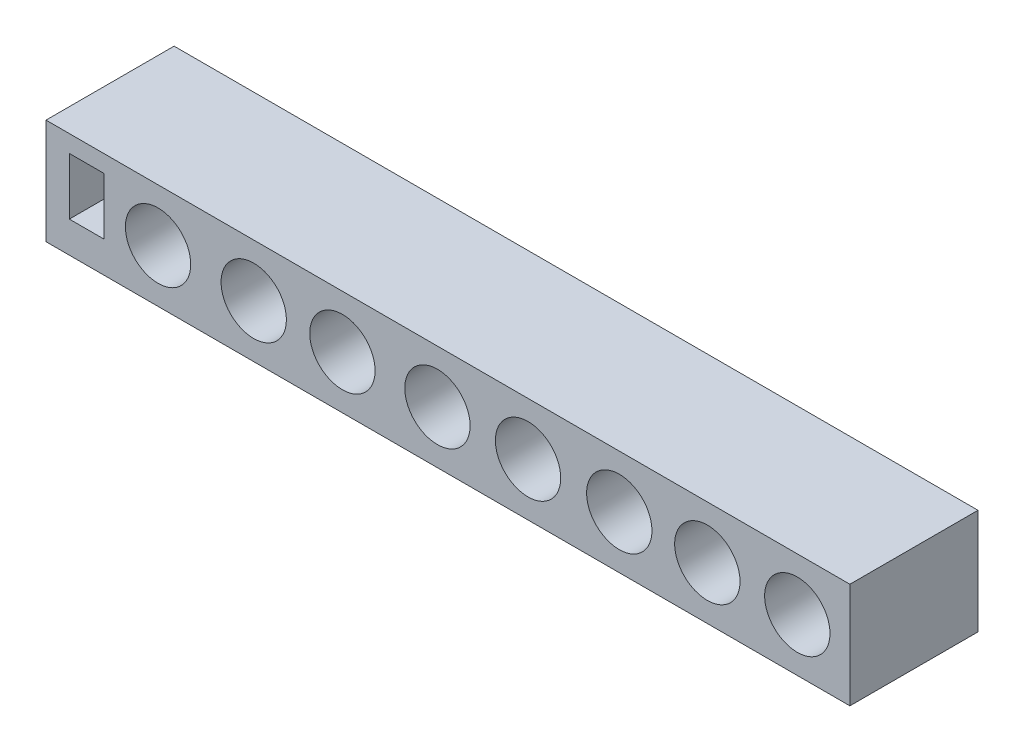
SolidWorks part; units mm, degrees
ref_plane "Front" through (0, 0, 0) normal (0, 0, 1) x (1, 0, 0)
ref_plane "Top" through (0, 0, 0) normal (0, 1, 0) x (1, 0, 0)
ref_plane "Right" through (0, 0, 0) normal (1, 0, 0) x (0, 0, -1)
sketch "Sketch1" plane through (0, 0, 0) normal (0, 0, 1) x (1, 0, 0)
  line L0 (62.7555, 4.1115) -> (0, 4.1115) construction
  line L1 (0, 0) -> (62.7555, 0)
  line L2 (0, 0) -> (0, 8.2229)
  line L3 (0, 8.2229) -> (62.7555, 8.2229)
  line L4 (62.7555, 0) -> (62.7555, 8.2229)
  line L5 (4.5117, 6.8812) -> (1.8222, 6.8812)
  line L6 (4.5117, 6.8812) -> (4.5117, 2.4417)
  line L7 (4.5117, 2.4417) -> (1.8222, 2.4417)
  line L8 (1.8222, 6.8812) -> (1.8222, 2.4417)
  circle A0 centre (8.7465, 4.1115) radius 2.8
  circle A1 centre (16.2148, 4.1115) radius 2.775
  circle A2 centre (23.139, 4.1115) radius 2.75
  circle A3 centre (30.5578, 4.1115) radius 2.725
  circle A4 centre (37.6304, 4.1115) radius 2.825
  circle A5 centre (44.7525, 4.1115) radius 2.85
  circle A6 centre (51.6273, 4.1115) radius 2.875
  circle A7 centre (58.6505, 4.1115) radius 2.9
  circle A10 centre (8.7465, 4.1115) radius 2.55
  circle A11 centre (16.2148, 4.1115) radius 2.55
  circle A12 centre (23.139, 4.1115) radius 2.55
  circle A13 centre (30.5578, 4.1115) radius 2.55
  circle A14 centre (37.6304, 4.1115) radius 2.55
  circle A15 centre (44.7525, 4.1115) radius 2.55
  circle A16 centre (51.6273, 4.1115) radius 2.55
  circle A17 centre (58.6505, 4.1115) radius 2.55
  dimension "D1" = 5.6
  dimension "D2" = 5.55
  dimension "D3" = 5.5
  dimension "D4" = 5.45
  dimension "D5" = 5.65
  dimension "D6" = 5.7
  dimension "D7" = 5.75
  dimension "D8" = 5.8
  dimension "D9" = 5.1
extrude "Boss-Extrude1" add sketch "Sketch1" along normal blind 10 contours L3 L4 L1 L2
extrude "Cut-Extrude1" cut sketch "Sketch1<3>" along normal blind 10 contours A17 L0 | L0 A17 | L0 A16 | A16 L0 | L0 A15 | A15 L0 | L0 A14 | A14 L0 | A13 L0 | L0 A13 | L0 A12 | A12 L0 | L0 A11 | A11 L0 | L0 A10 | A10 L0 | L0 L6 L5 L8 | L6 L0 L8 L7 region at (58.6505, 3.0292, 0) region at (58.6505, 5.1937, 0) region at (51.6273, 3.0292, 0) region at (51.6273, 5.1937, 0) region at (3.1669, 5.4963, 0) region at (3.1669, 3.2766, 0) region at (44.7525, 3.0292, 0) region at (44.7525, 5.1937, 0) region at (8.7465, 5.1937, 0) region at (8.7465, 3.0292, 0) region at (37.6304, 3.0292, 0) region at (37.6304, 5.1937, 0) region at (16.2148, 5.1937, 0) region at (16.2148, 3.0292, 0) region at (30.5578, 3.0292, 0) region at (30.5578, 5.1937, 0) region at (23.139, 5.1937, 0) region at (23.139, 3.0292, 0)
sketch "Sketch1<3>" plane through (0, 0, 0) normal (0, 0, 1) x (1, 0, 0) same geometry as "Sketch1"
extrude "Cut-Extrude2" cut sketch "Sketch1<4>" along normal blind 1.2 contours A7 | A6 | A5 | A4 | A3 | A2 | A1 | A0
sketch "Sketch1<4>" plane through (0, 0, 0) normal (0, 0, 1) x (1, 0, 0) same geometry as "Sketch1"
